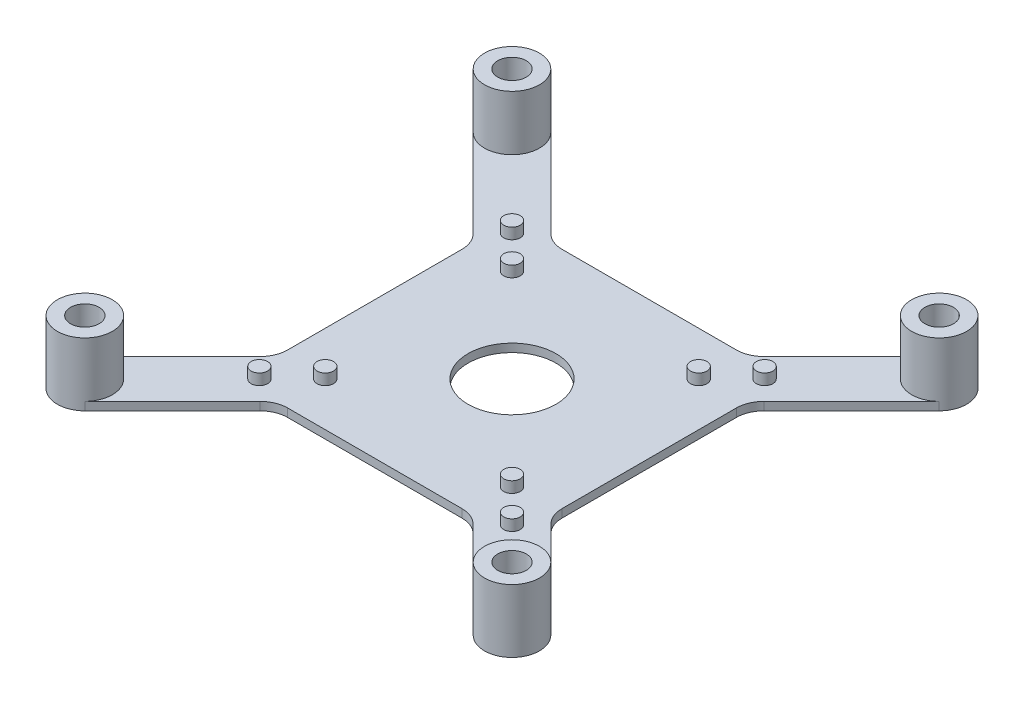
SolidWorks part; units mm, degrees
ref_plane "Front Plane" through (0, 0, 0) normal (0, 0, 1) x (1, 0, 0)
ref_plane "Top Plane" through (0, 0, 0) normal (0, 1, 0) x (1, 0, 0)
ref_plane "Right Plane" through (0, 0, 0) normal (1, 0, 0) x (0, 0, -1)
sketch "Sketch1" plane through (0, 0, 0) normal (0, 1, 0) x (1, 0, 0)
  line L1 (-25, -25) -> (25, -25)
  line L2 (-25, -25) -> (-25, 25)
  line L3 (-25, 25) -> (25, 25)
  line L4 (25, -25) -> (25, 25)
  line L5 (-25, -25) -> (25, 25) construction
  line L6 (-25, 25) -> (25, -25) construction
  circle A0 centre (0, 0) radius 8
  point P0 (0, 0)
  dimension "D2" = 16
  dimension "D1" = 50
extrude "Boss-Extrude1" add sketch "Sketch1" along normal blind 1.5
sketch "Sketch3" plane through (0, 1.5, 0) normal (0, 1, 0) x (1, 0, 0)
  line L0 (0, 0) -> (0, -6.5515) construction
  line L1 (-23, -25) -> (-15, -25)
  line L2 (-25, -23) -> (-25, -15)
  line L3 (-25, -15) -> (-17, -15)
  line L4 (-15, -25) -> (-15, -17)
  line L5 (0, -6.5515) -> (0, 0) construction
  line L6 (0, 0) -> (-7.2066, 0) construction
  line L7 (-25, 15) -> (-17, 15)
  line L8 (-15, 25) -> (-15, 17)
  line L9 (-23, 25) -> (-15, 25)
  line L10 (-25, 23) -> (-25, 15)
  line L11 (25, -15) -> (17, -15)
  line L12 (15, -25) -> (15, -17)
  line L13 (23, -25) -> (15, -25)
  line L14 (25, -23) -> (25, -15)
  line L15 (25, 23) -> (25, 15)
  line L16 (23, 25) -> (15, 25)
  line L17 (15, 25) -> (15, 17)
  line L18 (25, 15) -> (17, 15)
  arc A0 (23, -25) -> (25, -23) centre (23, -23) ccw
  arc A1 (25, 23) -> (23, 25) centre (23, 23) ccw
  arc A2 (-23, 25) -> (-25, 23) centre (-23, 23) ccw
  arc A3 (-23, -25) -> (-25, -23) centre (-23, -23) cw
  arc A4 (17, -15) -> (15, -17) centre (17, -17) ccw
  arc A5 (15, 17) -> (17, 15) centre (17, 17) ccw
  arc A6 (-17, 15) -> (-15, 17) centre (-17, 17) ccw
  arc A7 (-17, -15) -> (-15, -17) centre (-17, -17) cw
  circle A8 centre (-23, -23) radius 1.5
  circle A9 centre (-17, -17) radius 1.5
  circle A10 centre (23, -23) radius 1.5
  circle A11 centre (17, -17) radius 1.5
  circle A12 centre (23, 23) radius 1.5
  circle A13 centre (17, 17) radius 1.5
  circle A14 centre (-23, 23) radius 1.5
  circle A15 centre (-17, 17) radius 1.5
  point P23 (25, -25)
  point P26 (25, 25)
  point P29 (-25, 25)
  point P32 (-25, -25)
  point P35 (15, -15)
  point P38 (15, 15)
  point P41 (-15, 15)
  point P44 (-15, -15)
  dimension "D2" = 2
  dimension "D3" = 3
  dimension "D1" = 10
sketch "Sketch4" plane through (0, 1.5, 0) normal (0, 1, 0) x (1, 0, 0)
  circle A0 centre (-23, 23) radius 1.5
  circle A1 centre (-17, 17) radius 1.5
  circle A3 centre (17, 17) radius 1.5
  circle A4 centre (23, 23) radius 1.5
  circle A5 centre (-17, -17) radius 1.5
  circle A6 centre (-23, -23) radius 1.5
  circle A7 centre (17, -17) radius 1.5
  circle A8 centre (23, -23) radius 1.5
  dimension "D1" = 3
extrude "Boss-Extrude2" add sketch "Sketch4" along normal blind 2
sketch "Sketch5" plane through (0, 1.5, 0) normal (0, 1, 0) x (1, 0, 0)
  line L0 (0, 0) -> (0, 33.3014) construction
  line L1 (0, 0) -> (36.9203, 0) construction
  line L2 (0, 0) -> (38.8909, 38.8909) construction
  line L3 (0, 0) -> (-38.8909, -38.8909) construction
  line L4 (-35.3553, -42.4264) -> (-42.4264, -35.3553) construction
  line L5 (42.4264, 35.3553) -> (35.3553, 42.4264) construction
  line L6 (-42.4264, -35.3553) -> (-25, -17.9289)
  line L7 (-25, 25) -> (-25, -25) construction
  line L8 (-35.3553, -42.4264) -> (-17.9289, -25)
  line L9 (-25, -25) -> (25, -25) construction
  line L10 (35.3553, 42.4264) -> (17.9289, 25)
  line L11 (25, 25) -> (-25, 25) construction
  line L12 (42.4264, 35.3553) -> (25, 17.9289)
  line L13 (25, -25) -> (25, 25) construction
  line L14 (-42.4264, -35.3553) -> (-45.9619, -38.8909)
  line L15 (-45.9619, -38.8909) -> (-38.8909, -45.9619)
  line L16 (-38.8909, -45.9619) -> (-35.3553, -42.4264)
  line L17 (35.3553, 42.4264) -> (38.8909, 45.9619)
  line L18 (38.8909, 45.9619) -> (45.9619, 38.8909)
  line L19 (45.9619, 38.8909) -> (42.4264, 35.3553)
  line L20 (45.9619, -38.8909) -> (42.4264, -35.3553)
  line L21 (35.3553, -42.4264) -> (38.8909, -45.9619)
  line L22 (38.8909, -45.9619) -> (45.9619, -38.8909)
  line L23 (42.4264, -35.3553) -> (25, -17.9289)
  line L24 (35.3553, -42.4264) -> (17.9289, -25)
  line L25 (-42.4264, 35.3553) -> (-45.9619, 38.8909)
  line L26 (-38.8909, 45.9619) -> (-35.3553, 42.4264)
  line L27 (-45.9619, 38.8909) -> (-38.8909, 45.9619)
  line L28 (-35.3553, 42.4264) -> (-17.9289, 25)
  line L29 (-42.4264, 35.3553) -> (-25, 17.9289)
  line L30 (-25, 17.9289) -> (-25, -17.9289)
  line L31 (-17.9289, -25) -> (17.9289, -25)
  line L32 (25, 17.9289) -> (25, -17.9289)
  line L33 (-17.9289, 25) -> (17.9289, 25)
  circle A0 centre (-38.8909, -38.8909) radius 2.6
  circle A1 centre (38.8909, 38.8909) radius 2.6
  circle A2 centre (38.8909, -38.8909) radius 2.6
  circle A3 centre (-38.8909, 38.8909) radius 2.6
  circle A4 centre (0, 0) radius 8 construction
  circle A5 centre (0, 0) radius 8
  point P9 (-38.8909, -38.8909)
  point P12 (38.8909, 38.8909)
  dimension "D6" = 5.2
  dimension "D1" = 45
  dimension "D2" = 55
  dimension "D3" = 10
  dimension "D4" = 5
  dimension "D5" = 5
extrude "Boss-Extrude3" add sketch "Sketch5" against normal blind 1.5
fillet "Fillet1" radius 5 16 edges at (17.9289, 0.75, 25) (38.8909, 0.75, 45.9619) (45.9619, 0.75, 38.8909) (25, 0.75, 17.9289) (25, 0.75, -17.9289) (45.9619, 0.75, -38.8909) (38.8909, 0.75, -45.9619) (17.9289, 0.75, -25) (-17.9289, 0.75, -25) (-38.8909, 0.75, -45.9619) (-45.9619, 0.75, -38.8909) (-25, 0.75, -17.9289) (-25, 0.75, 17.9289) (-45.9619, 0.75, 38.8909) (-38.8909, 0.75, 45.9619) (-17.9289, 0.75, 25)
sketch "Sketch6" plane through (0, 1.5, 0) normal (0, 1, 0) x (1, 0, 0)
  circle A0 centre (38.8909, -38.8909) radius 2.6 construction
  circle A1 centre (38.8909, 38.8909) radius 2.6 construction
  circle A2 centre (-38.8909, 38.8909) radius 2.6 construction
  circle A3 centre (-38.8909, -38.8909) radius 2.6 construction
  circle A4 centre (38.8909, -38.8909) radius 2.6
  circle A5 centre (38.8909, 38.8909) radius 2.6
  circle A6 centre (-38.8909, 38.8909) radius 2.6
  circle A7 centre (-38.8909, -38.8909) radius 2.6
  circle A8 centre (-38.8909, -38.8909) radius 5
  circle A9 centre (-38.8909, 38.8909) radius 5
  circle A10 centre (38.8909, 38.8909) radius 5
  circle A11 centre (38.8909, -38.8909) radius 5
extrude "Boss-Extrude4" add sketch "Sketch6" along normal blind 10
